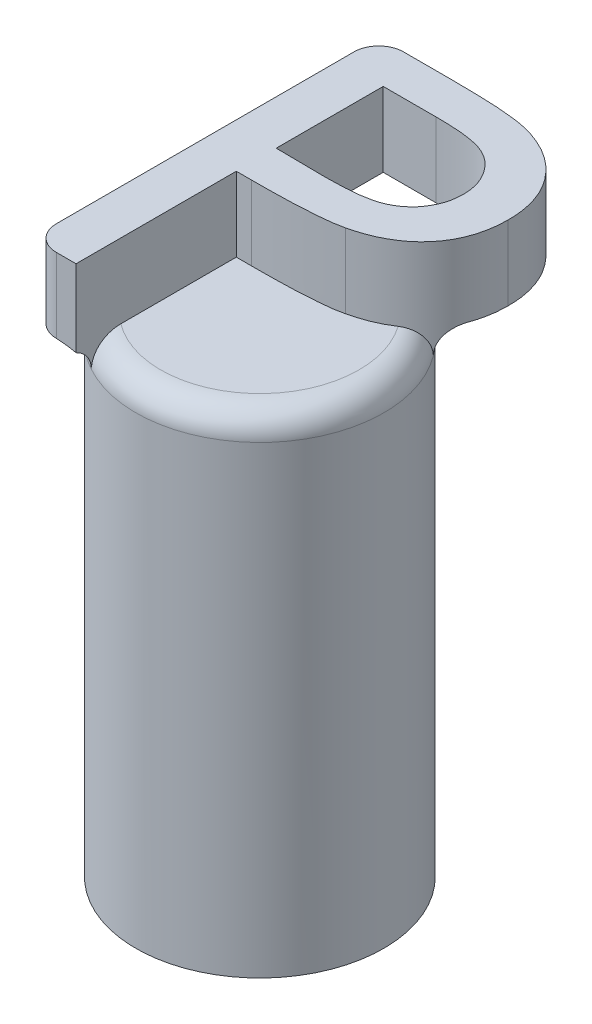
SolidWorks part; units mm, degrees
ref_plane "Ebene vorne" through (0, 0, 0) normal (0, 0, 1) x (1, 0, 0)
ref_plane "Ebene oben" through (0, 0, 0) normal (0, 1, 0) x (1, 0, 0)
ref_plane "Ebene rechts" through (0, 0, 0) normal (1, 0, 0) x (0, 0, -1)
sketch "Skizze1" plane through (0, 0, 0) normal (0, 1, 0) x (1, 0, 0)
  circle A0 centre (0, 0) radius 5
extrude "Aufsatz-Linear austragen2" add sketch "Skizze1" along normal blind 20
sketch "Skizze2" plane through (0, 20, 0) normal (0, 1, 0) x (1, 0, 0)
  circle A1 centre (0, 0) radius 5 construction
  text T0 "<b>P</b>" font "Century Gothic" height 14
  dimension "D2" = 6
  dimension "D1" = 5
sketch "Skizze3" plane through (0, 0, 0) normal (0, -1, 0) x (-1, 0, 0)
  circle A0 centre (0, 0) radius 4.5
extrude "Schnitt-Linear austragen1" cut sketch "Skizze3" against normal blind 1
chamfer "Fase1" distance 1 angle 31 1 edges at (0, 0, -4.5) first distance on face at (0, 0, -4.5)
sketch "Skizze4" plane through (0, 1, 0) normal (0, -1, 0) x (-1, 0, 0)
  circle A0 centre (0, 0) radius 1.55
extrude "Schnitt-Linear austragen3" cut sketch "Skizze4" against normal blind 18
extrude "Aufsatz-Linear austragen4" add sketch "Skizze2" along normal blind 3
fillet "Verrundung2" radius 1 3 edges at (-3.4122, 20, 3.6547) (3.4175, 20, -3.6497) (-3.4122, 20, -3.6547)
fillet "Verrundung3" radius 1 3 edges at (3.7669, 20, 3.288) (0.1746, 20, -4.9969) (-5, 20, 0)
fillet "Verrundung4" radius 1 2 edges at (-4.2051, 21.5, -9) (-4.2051, 21.5, 5)
